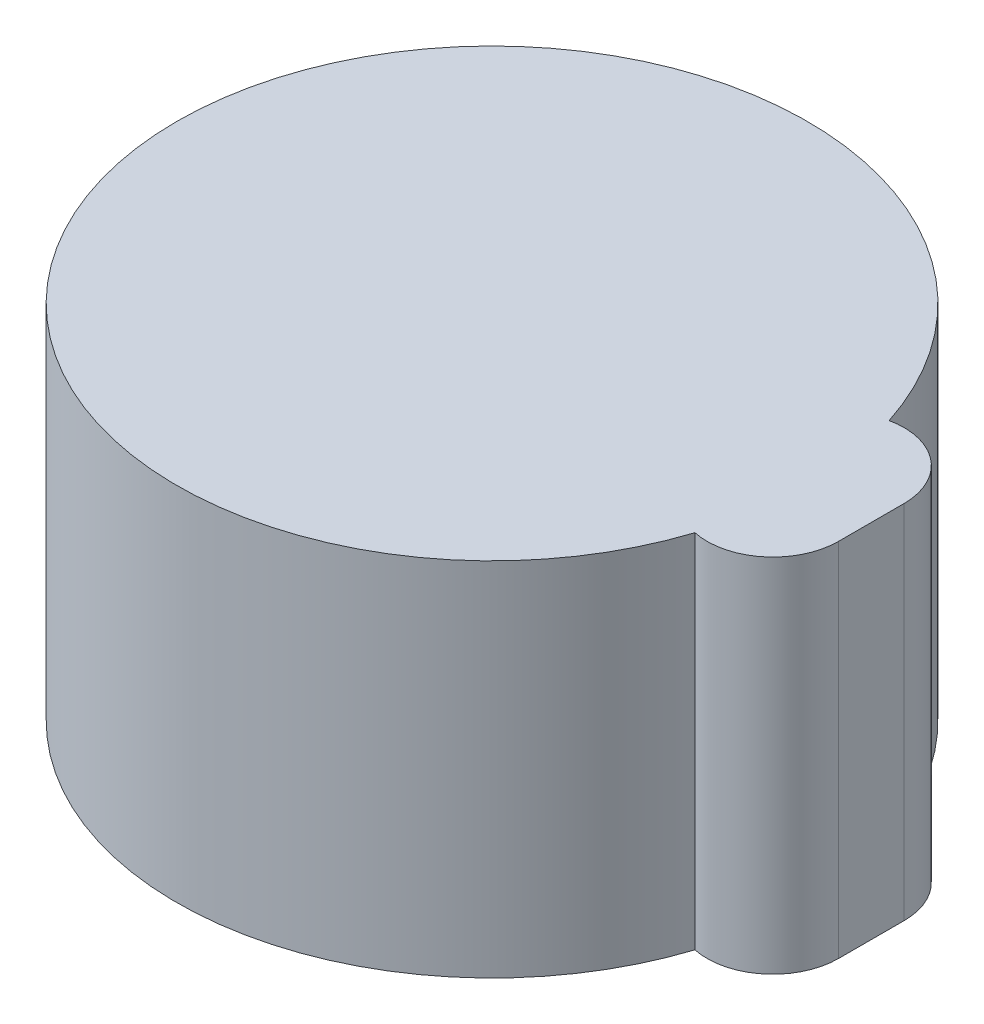
SolidWorks part; units mm, degrees
ref_plane "Front Plane" through (0, 0, 0) normal (0, 0, 1) x (1, 0, 0)
ref_plane "Top Plane" through (0, 0, 0) normal (0, 1, 0) x (1, 0, 0)
ref_plane "Right Plane" through (0, 0, 0) normal (1, 0, 0) x (0, 0, -1)
sketch "Sketch1" plane through (0, 0, 0) normal (0, 1, 0) x (1, 0, 0)
  line L0 (-6.6188, 0) -> (7.2814, 0) construction
  line L1 (5.2739, 0.5) -> (5.7739, 0.5) construction
  line L2 (0, 4.3) -> (0, 4.8) construction
  line L3 (5.7739, 0.5) -> (5.7739, -0.5)
  line L4 (4.696, 0.9939) -> (4.1836, 0.9939)
  line L5 (4.696, -0.9939) -> (4.1836, -0.9939)
  line L6 (5.2739, 0.5) -> (5.2739, -0.5)
  circle A0 centre (0, 0) radius 4.3
  circle A1 centre (0, 0) radius 4.8
  circle A2 centre (4.7739, 0.5) radius 0.5
  circle A3 centre (4.7739, -0.5) radius 0.5
  circle A4 centre (4.7739, 0.5) radius 1
  circle A5 centre (4.7739, -0.5) radius 1
  dimension "D1" = 8.6
  dimension "D2" = 0.5
  dimension "D3" = 1
extrude "Boss-Extrude1" add sketch "Sketch1" along normal blind 5 contours A5 A0 A4 A1 | A1 A4 A0 A2 | A5 A4 A1 A2 L6 | A4 A5 L6 | A5 L3 A4 | A5 A4 L6 A3 A1 | A0 A5 A1 A3 region at (5.273, 0, -0.897) region at (5.7342, 0, 0) region at (5.273, 0, 0.897) region at (4.2656, 0, -1.5138) region at (4.4131, 0, -1.1963) region at (5.4065, 0, 0) region at (4.4131, 0, 1.1963)
sketch "Sketch3" plane through (0, 5, 0) normal (0, 1, 0) x (1, 0, 0)
  line L1 (5.7739, -0.5) -> (5.7739, 0.5)
  line L2 (5.7739, -0.5) -> (5.7739, 0.5)
  arc A3 (4.5667, -1.4783) -> (5.7739, -0.5) centre (4.7739, -0.5) ccw
  arc A4 (5.7739, 0.5) -> (4.5667, 1.4783) centre (4.7739, 0.5) ccw
  arc A5 (4.5667, 1.4783) -> (4.5667, -1.4783) centre (0, 0) ccw
  arc A6 (4.5667, -1.4783) -> (5.7739, -0.5) centre (4.7739, -0.5) ccw
  arc A7 (5.7739, 0.5) -> (4.5667, 1.4783) centre (4.7739, 0.5) ccw
  arc A8 (4.5667, 1.4783) -> (4.5667, -1.4783) centre (0, 0) ccw
  dimension "D1" = 0
extrude "Boss-Extrude2" add sketch "Sketch3" along normal blind 0.5
sketch "Sketch4" plane through (0, 5, 0) normal (0, -1, 0) x (1, 0, 0)
  line L0 (4.1836, 0.9939) -> (3.6677, 0.9939)
  line L1 (4.1836, -0.9939) -> (3.6677, -0.9939)
  circle A0 centre (0, 0) radius 3.8
  arc A1 (4.1836, 0.9939) -> (4.1836, -0.9939) centre (0, 0) ccw construction
  arc M6 (4.1836, 0.9939) -> (4.1836, -0.9939) centre (0, 0) ccw
  dimension "D1" = 0.5
extrude "Boss-Extrude3" add sketch "Sketch4" along normal blind 1 contours A0 M6 region at (3.9256, 5, 1.1147)
sketch "Sketch5" plane through (0, 4, 0) normal (0, -1, 0) x (1, 0, 0)
  line L0 (0, 4.3) -> (0, -4.3) construction
  line L1 (3.0406, -3.0406) -> (-3.0406, 3.0406) construction
  line L2 (-3.0406, -3.0406) -> (3.0406, 3.0406) construction
  arc A0 (4.1836, 0.9939) -> (4.1836, -0.9939) centre (0, 0) ccw construction
  arc A1 (4.1836, 0.9939) -> (4.1836, -0.9939) centre (0, 0) ccw construction
  circle A2 centre (3.0406, 3.0406) radius 0.25
  circle A3 centre (-3.0406, 3.0406) radius 0.25
  circle A4 centre (-3.0406, -3.0406) radius 0.25
  circle A5 centre (3.0406, -3.0406) radius 0.25
  dimension "D2" = 0.5
  dimension "D1" = 45
extrude "Boss-Extrude4" [suppressed] add sketch "Sketch5" along normal up to surface (4 mm away) up to face at (2.9452, 0, 0)
